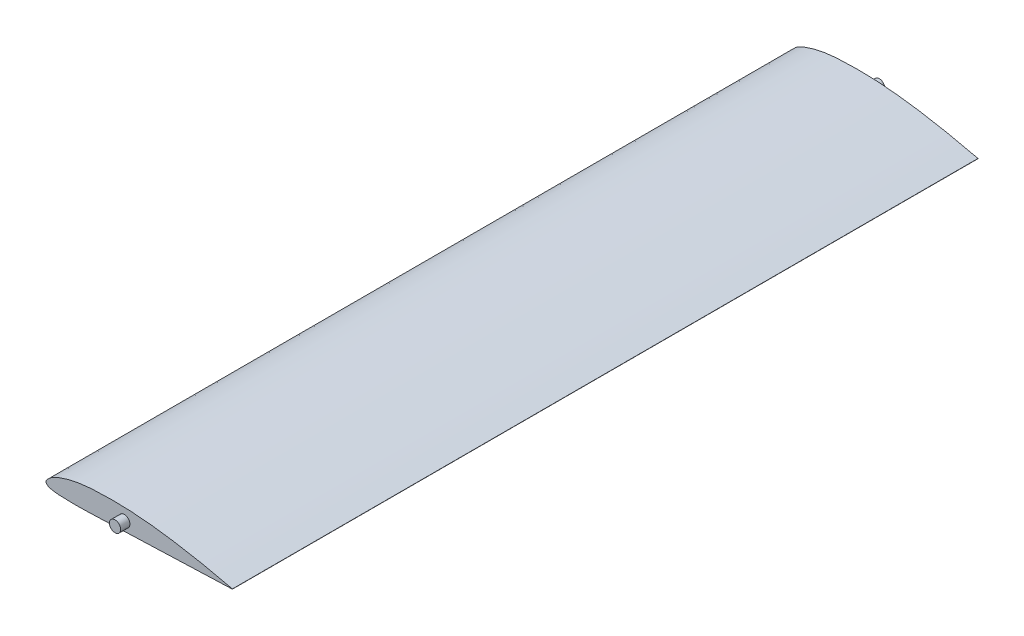
SolidWorks part; units mm, degrees
ref_plane "Front Plane" through (0, 0, 0) normal (0, 0, 1) x (1, 0, 0)
ref_plane "Top Plane" through (0, 0, 0) normal (0, 1, 0) x (1, 0, 0)
ref_plane "Right Plane" through (0, 0, 0) normal (1, 0, 0) x (0, 0, -1)
other "Center of Mass"
curve "Curve2"
  spline degree 3 poles (100, 0.0599, 0) (99.6667, 0.1389, 0) (99.0001, 0.297, 0) (98.0001, 0.5335, 0) (97.0002, 0.7689, 0) (95.6673, 1.0805, 0) (94.0012, 1.464, 0) (92.0011, 1.913, 0) (90.001, 2.3517, 0) (88.001, 2.7804, 0) (86.001, 3.1989, 0) (84.0011, 3.607, 0) (82.0011, 4.0041, 0) (80.0011, 4.3901, 0) (78.001, 4.7646, 0) (76.001, 5.1274, 0) (74.001, 5.4786, 0) (72.001, 5.8178, 0) (70.0009, 6.1451, 0) (68.001, 6.4605, 0) (66.001, 6.7627, 0) (64.0011, 7.0506, 0) (62.0011, 7.3232, 0) (60.0011, 7.5792, 0) (58.001, 7.8174, 0) (56.0009, 8.0377, 0) (54.0009, 8.24, 0) (52.0008, 8.4244, 0) (50.0007, 8.5907, 0) (48.0007, 8.7389, 0) (46.0006, 8.8677, 0) (44.0005, 8.9755, 0) (42.0004, 9.0606, 0) (40.0003, 9.1215, 0) (38.0001, 9.1562, 0) (36, 9.1664, 0) (33.9999, 9.1542, 0) (31.9998, 9.1217, 0) (29.9998, 9.0706, 0) (27.9995, 9.0041, 0) (25.9991, 8.914, 0) (23.9984, 8.7902, 0) (21.9974, 8.623, 0) (19.9961, 8.4023, 0) (17.995, 8.1169, 0) (15.9942, 7.7664, 0) (13.9928, 7.3531, 0) (11.9902, 6.8729, 0) (9.9867, 6.312, 0) (7.9834, 5.6534, 0) (6.3159, 5.0243, 0) (4.987, 4.4324, 0) (3.9799, 3.9169, 0) (2.9638, 3.3042, 0) (2.0257, 2.5894, 0) (1.3212, 1.9111, 0) (0.7834, 1.3659, 0) (0.4419, 0.9673, 0) (0.2174, 0.6242, 0) (0.1075, 0.3995, 0) (0.0374, 0.2059, 0) (-0.0262, -0.0739, 0) (0.0061, -0.365, 0) (0.1075, -0.6183, 0) (0.2162, -0.8198, 0) (0.4373, -1.1135, 0) (0.7742, -1.4249, 0) (1.2999, -1.7806, 0) (2.0457, -2.0688, 0) (2.9972, -2.2604, 0) (3.9964, -2.4592, 0) (4.9972, -2.6119, 0) (6.3307, -2.7532, 0) (7.9992, -2.8493, 0) (9.9993, -2.9441, 0) (11.9997, -3.0014, 0) (13.9999, -3.0284, 0) (16.0001, -3.0291, 0) (18.0001, -3.0079, 0) (20.0002, -2.9688, 0) (22.0002, -2.9162, 0) (24.0001, -2.8531, 0) (26.0001, -2.7824, 0) (28, -2.7072, 0) (30, -2.6305, 0) (32, -2.5554, 0) (34, -2.4816, 0) (36, -2.4086, 0) (38, -2.3361, 0) (40, -2.2635, 0) (42, -2.1905, 0) (44, -2.1171, 0) (46, -2.0436, 0) (48, -1.9699, 0) (50, -1.8962, 0) (52, -1.8226, 0) (54, -1.7491, 0) (56, -1.6757, 0) (58, -1.6023, 0) (60, -1.5289, 0) (62, -1.4555, 0) (64, -1.3821, 0) (66, -1.3086, 0) (68, -1.2351, 0) (70, -1.1617, 0) (72, -1.0882, 0) (74, -1.0148, 0) (76, -0.9413, 0) (78, -0.8679, 0) (80, -0.7944, 0) (82, -0.721, 0) (84, -0.6475, 0) (86, -0.5741, 0) (88, -0.5006, 0) (90, -0.4272, 0) (92, -0.3537, 0) (94, -0.2803, 0) (95.6667, -0.2191, 0) (97, -0.1701, 0) (98, -0.1334, 0) (99, -0.0967, 0) (99.6667, -0.0722, 0) (100, -0.0599, 0) knots 0 0 0 0 0.005028 0.010055 0.015081 0.020105 0.030145 0.040174 0.050191 0.060198 0.070194 0.08018 0.090156 0.100121 0.110076 0.12002 0.129954 0.139879 0.149793 0.159699 0.169594 0.17948 0.189355 0.199219 0.209073 0.218917 0.228751 0.238577 0.248396 0.258207 0.268012 0.277811 0.287604 0.297393 0.307179 0.316964 0.326749 0.336535 0.346322 0.356113 0.365908 0.375711 0.385531 0.395376 0.405259 0.415192 0.425184 0.435248 0.445412 0.455711 0.466191 0.471552 0.477054 0.482787 0.488946 0.494316 0.497126 0.500187 0.502001 0.503128 0.50385 0.50502 0.507318 0.507986 0.509024 0.510668 0.513358 0.515716 0.519949 0.524973 0.529954 0.534903 0.539824 0.54963 0.559425 0.569214 0.579 0.588784 0.59857 0.608356 0.618144 0.627933 0.637724 0.647515 0.657307 0.667099 0.67689 0.686681 0.696472 0.706263 0.716054 0.725846 0.735637 0.745428 0.755219 0.765011 0.774802 0.784593 0.794384 0.804176 0.813967 0.823758 0.833549 0.84334 0.853132 0.862923 0.872714 0.882505 0.892297 0.902088 0.911879 0.92167 0.931461 0.941253 0.951044 0.960835 0.970626 0.980418 0.985313 0.990209 0.995104 1 1 1 1
sketch "Sketch7" plane through (0, 0, 0) normal (0, 0, 1) x (1, 0, 0)
  line L0 (100, 0.0599) -> (100, -0.0599)
  line L1 (0, 0) -> (100, 0) construction
  line L2 (0, 0) -> (0, 2.6099) construction
  spline S1 degree 3 poles (100, 0.0599) (99.6667, 0.1389) (99.0001, 0.297) (98.0003, 0.5335) (97.0004, 0.7689) (95.6676, 1.0804) (94.0016, 1.4639) (92.0016, 1.9129) (90.0017, 2.3515) (88.0018, 2.7802) (86.0019, 3.1987) (83.3368, 3.7424) (79.3412, 4.525) (75.3393, 5.2515) (72.0027, 5.8175) (69.3375, 6.2536) (66.6711, 6.6661) (64.0033, 7.0502) (62.0035, 7.3227) (59.3383, 7.6638) (56.6716, 7.9696) (54.0037, 8.2395) (52.0038, 8.4239) (50.0038, 8.5901) (48.0039, 8.7384) (46.004, 8.8672) (44.0041, 8.9749) (42.0041, 9.06) (40.0041, 9.1209) (38.004, 9.1556) (36.004, 9.1658) (34.004, 9.1536) (32.0041, 9.1211) (30.0041, 9.07) (28.0041, 9.0035) (26.0037, 8.9134) (24.0032, 8.7897) (22.0023, 8.6224) (20.0011, 8.4018) (18.0001, 8.1164) (15.9994, 7.7659) (13.9982, 7.3526) (11.9957, 6.8724) (9.9923, 6.3116) (7.9892, 5.6531) (6.3218, 5.024) (4.993, 4.4322) (3.986, 3.9166) (2.9699, 3.304) (2.0319, 2.5893) (1.3274, 1.911) (0.7897, 1.3658) (0.4482, 0.9672) (0.2237, 0.6241) (0.1138, 0.3995) (0.0436, 0.2059) (-0.0199, -0.0739) (0.0124, -0.3649) (0.1137, -0.6183) (0.2225, -0.8198) (0.4436, -1.1134) (0.7805, -1.4248) (1.306, -1.7805) (2.0518, -2.0687) (3.0033, -2.2602) (4.0025, -2.459) (5.0031, -2.6118) (6.3365, -2.753) (8.0049, -2.8491) (10.005, -2.9439) (12.0052, -3.0012) (14.0053, -3.0283) (16.0053, -3.0289) (18.0053, -3.0077) (20.0052, -2.9686) (22.005, -2.916) (24.6717, -2.8318) (27.338, -2.7326) (30.0044, -2.6304) (32.6708, -2.5303) (35.3374, -2.4327) (38.0039, -2.3359) (40.0038, -2.2633) (42.0036, -2.1903) (44.0035, -2.117) (46.67, -2.0189) (50.0031, -1.896) (53.3363, -1.7735) (56.0028, -1.6756) (58.0026, -1.6022) (60.6691, -1.5044) (63.3356, -1.4065) (66.0021, -1.3085) (68.002, -1.2351) (70.0019, -1.1616) (72.0018, -1.0882) (79.3346, -0.8189) (86.6675, -0.5496) (94.3337, -0.268) (96.3336, -0.1946) (98.3334, -0.1211) (99.3334, -0.0844) (100, -0.0599) knots 0 0 0 0 0.005028 0.010055 0.015081 0.020105 0.030145 0.040174 0.050191 0.060198 0.070194 0.08018 0.100121 0.129954 0.139879 0.149793 0.169594 0.17948 0.189355 0.199219 0.218917 0.228751 0.238577 0.248396 0.258207 0.268012 0.277811 0.287604 0.297393 0.307179 0.316964 0.326749 0.336535 0.346322 0.356113 0.365908 0.375711 0.385531 0.395376 0.405259 0.415192 0.425184 0.435248 0.445412 0.455711 0.466191 0.471552 0.477054 0.482787 0.488946 0.494316 0.497126 0.500187 0.502001 0.503128 0.50385 0.50502 0.507318 0.507986 0.509024 0.510668 0.513358 0.515716 0.519949 0.524973 0.529954 0.534903 0.539824 0.54963 0.559425 0.569214 0.579 0.588784 0.59857 0.608356 0.618144 0.627933 0.647515 0.657307 0.667099 0.686681 0.696472 0.706263 0.716054 0.725846 0.735637 0.755219 0.774802 0.784593 0.794384 0.804176 0.823758 0.833549 0.84334 0.853132 0.862923 0.872714 0.960835 0.970626 0.985313 0.990209 1 1 1 1
  dimension "D1" = 100
extrude "Boss-Extrude4" add sketch "Sketch7" along normal mid plane 400 contours S1 L0
other "Center of Mass Reference Point"
sketch "Sketch8" plane through (0, 0, 0) normal (0, 0, 1) x (1, 0, 0)
  circle A0 centre (42.0369, 2.6692) radius 3
  point P2 (0, 0)
  point P3 (19.8983, 1.368)
  point P4 (0, 0)
  point P5 (20.3615, 1.2638)
  point P6 (0, 0)
  point P7 (21.1023, 1.2451)
  point P8 (0, 0)
  point P9 (26.4219, -1.5826)
  dimension "D1" = 0
  dimension "D3" = 6
  dimension "D2" = 0
extrude "Boss-Extrude5" add sketch "Sketch8" along normal blind 5 from surface starting at face at (100, 0.03, 200)
mirror "Mirror1" about plane through (0, 0, 0) normal (0, 0, 1) of "Boss-Extrude5"
